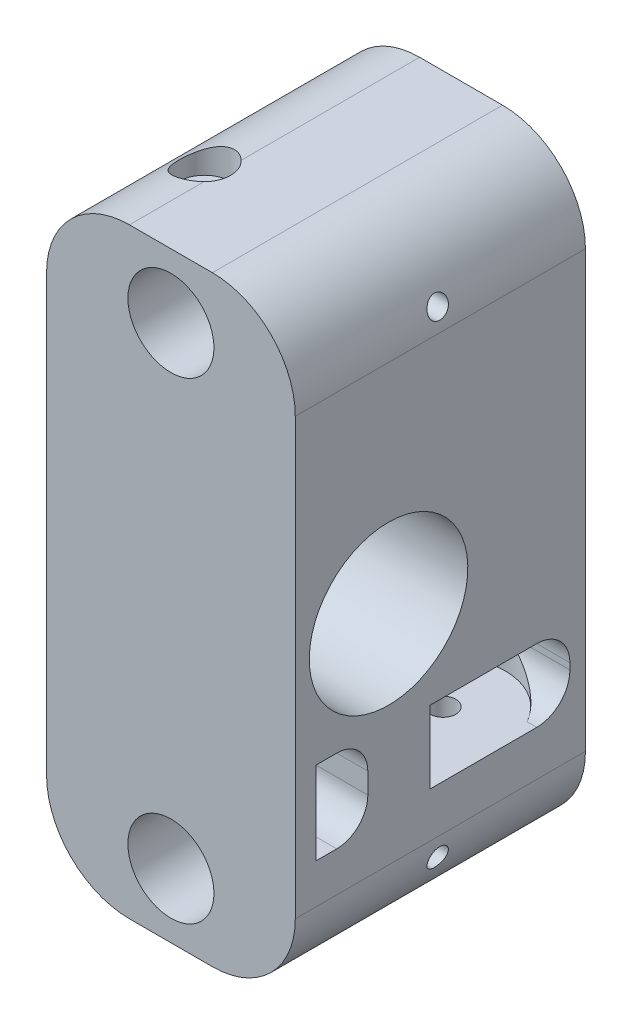
SolidWorks part; units mm, degrees
ref_plane "前视基准面" through (0, 0, 0) normal (0, 0, 1) x (1, 0, 0)
ref_plane "上视基准面" through (0, 0, 0) normal (0, 1, 0) x (1, 0, 0)
ref_plane "右视基准面" through (0, 0, 0) normal (1, 0, 0) x (0, 0, -1)
sketch "草图1" plane through (0, 0, 0) normal (0, 0, 1) x (1, 0, 0)
  line L1 (-12, 29) -> (12, 29)
  line L2 (-12, 29) -> (-12, -29)
  line L3 (-12, -29) -> (12, -29)
  line L4 (12, 29) -> (12, -29)
  line L5 (-12, 29) -> (12, -29) construction
  line L6 (-12, -29) -> (12, 29) construction
  point P0 (0, 0)
  dimension "D1" = 24
  dimension "D2" = 58
extrude "凸台-拉伸1" add sketch "草图1" along normal mid plane 38
sketch "草图2" plane through (12, 0, 0) normal (1, 0, 0) x (0, 0, -1)
  circle A0 centre (0, 0) radius 7.65
  dimension "D1" = 15.3
extrude "切除-拉伸1" cut sketch "草图2" against normal through all
ref_plane "基准面1" through (0, 13.15, 0) normal (0, 1, 0) x (1, 0, 0)
ref_plane "基准面2" through (0, -13.15, 0) normal (0, 1, 0) x (1, 0, 0)
sketch "草图3" plane through (0, 13.15, 0) normal (0, 1, 0) x (1, 0, 0)
  line L0 (0, 0) -> (0, -24.6721) construction
  line L1 (0, 0) -> (-19.2514, 0) construction
  line L2 (-5.75, -7.5) -> (-12, -7.5)
  line L3 (-12, -19) -> (-12, 19) construction
  line L4 (-12, -7.5) -> (-12, 19)
  line L5 (-12, 19) -> (1.75, 19)
  line L6 (12, 19) -> (-12, 19) construction
  line L7 (1.75, 19) -> (1.75, 0)
  circle A2 centre (-5.75, 0) radius 6.5 construction
  circle A3 centre (-5.75, 0) radius 5 construction
  arc A4 (-5.75, -7.5) -> (1.75, 0) centre (-5.75, 0) ccw
  dimension "D1" = 13
  dimension "D2" = 10
  dimension "D3" = 5.75
  dimension "D4" = 15
extrude "切除-拉伸2" cut sketch "草图3" against normal mid plane 7
sketch "草图4" plane through (-12, 0, 0) normal (-1, 0, 0) x (0, 0, 1)
  line L0 (13.2, -13.15) -> (-13.2, -13.15) construction
  line L1 (2, -9.15) -> (7, -9.15)
  line L2 (2, -9.15) -> (2, -17.15)
  line L3 (2, -17.15) -> (7, -17.15)
  line L4 (7, -9.15) -> (7, -17.15)
  line L5 (2, -9.15) -> (7, -17.15) construction
  line L6 (2, -17.15) -> (7, -9.15) construction
  line L7 (0, 0) -> (0, -29.9749) construction
  circle A0 centre (0, -13.15) radius 5 construction
  circle A1 centre (0, -13.15) radius 6.5 construction
  point P0 (4.5, -13.15)
  dimension "D1" = 10
  dimension "D2" = 13
  dimension "D3" = 5
  dimension "D4" = 8
  dimension "D5" = 4.5
extrude "切除-拉伸3" cut sketch "草图4" against normal through all
sketch "草图5" plane through (0, -13.15, 0) normal (0, 1, 0) x (1, 0, 0)
  line L0 (0, 0) -> (0, 26.819) construction
  line L1 (0, 0) -> (24.2805, 0) construction
  line L2 (0, 6.5) -> (23.2538, 6.5) construction
  line L3 (5.75, 4) -> (12, 4)
  line L4 (12, -19) -> (12, 19) construction
  line L5 (-1.75, 11.5) -> (-1.75, 19)
  line L6 (-12, 19) -> (12, 19) construction
  line L7 (-1.75, 19) -> (12, 19)
  line L8 (12, 19) -> (12, 4)
  circle A0 centre (5.75, 11.5) radius 5 construction
  circle A1 centre (5.75, 11.5) radius 6.5 construction
  arc A2 (-1.75, 11.5) -> (5.75, 4) centre (5.75, 11.5) ccw
  dimension "D2" = 10
  dimension "D3" = 13
  dimension "D5" = 15
  dimension "D1" = 6.5
  dimension "D4" = 5.75
extrude "切除-拉伸4" cut sketch "草图5" against normal mid plane 7
sketch "草图6" plane through (0, 0, -19) normal (0, 0, -1) x (-1, 0, 0)
  line L0 (0, 0) -> (0, 34.6715) construction
  line L1 (0, 0) -> (21.1433, 0) construction
  line L4 (-1.75, 16.65) -> (5.75, 16.65) construction
  circle A0 centre (0, 22.8) radius 4.15
  circle A1 centre (0, -22.8) radius 4.15
  point P2 (0, 22.7298)
  point P6 (0, 22.7298)
  point P8 (2.4518, 16.65)
  point P9 (0, 0)
  dimension "D1" = 8.3
  dimension "D2" = 0
  dimension "D3" = 6.15
extrude "切除-拉伸5" cut sketch "草图6" against normal through all
sketch "草图7" plane through (0, 29, 0) normal (0, 1, 0) x (1, 0, 0)
  line L1 (-17.4244, -25.1168) -> (22.3506, -25.1168)
  line L2 (-17.4244, -25.1168) -> (-17.4244, -9)
  line L3 (-17.4244, -9) -> (22.3506, -9)
  line L4 (22.3506, -25.1168) -> (22.3506, -9)
  dimension "D1" = 9
extrude "切除-拉伸6" cut sketch "草图7" against normal through all
sketch "草图8" plane through (0, -29, 0) normal (0, -1, 0) x (1, 0, 0)
  circle A0 centre (5.75, -11.5) radius 1.25
  arc A1 (5.75, -4) -> (-1.75, -11.5) centre (5.75, -11.5) ccw construction
  dimension "D1" = 2.5
extrude "切除-拉伸7" cut sketch "草图8" against normal blind 22
sketch "草图9" plane through (0, 29, 0) normal (0, 1, 0) x (1, 0, 0)
  circle A0 centre (-5.75, 0) radius 1.25
  arc A1 (-5.75, -7.5) -> (1.75, 0) centre (-5.75, 0) ccw construction
  dimension "D1" = 2.5
extrude "切除-拉伸8" cut sketch "草图9" against normal blind 22
fillet "圆角1" radius 8 4 edges at (12, -29, -5) (-12, -29, -5) (-12, 29, -5) (12, 29, -5)
sketch "草图11" plane through (0, -29, 0) normal (0, -1, 0) x (1, 0, 0)
  circle A0 centre (5.75, -11.5) radius 2.5
  circle A1 centre (5.75, -11.5) radius 1.25 construction
  dimension "D1" = 5
extrude "切除-拉伸9" cut sketch "草图11" against normal blind 3
sketch "草图12" plane through (0, 29, 0) normal (0, 1, 0) x (1, 0, 0)
  circle A0 centre (-5.75, 0) radius 2.5
  circle A1 centre (-5.75, 0) radius 1.25 construction
  dimension "D1" = 5
extrude "切除-拉伸10" cut sketch "草图12" against normal blind 3
sketch "草图13" plane through (-12, 0, 0) normal (-1, 0, 0) x (0, 0, 1)
  line L0 (0, 0) -> (-22.1939, 0) construction
  line L1 (0, 0) -> (0, -35.0733) construction
  circle A0 centre (-5, -23) radius 1
  circle A1 centre (-5, 23) radius 1
  point P8 (-12.8729, -15.3558)
  point P9 (-9.2281, -11.3525)
  dimension "D1" = 2
  dimension "D2" = 5
  dimension "D3" = 23
extrude "切除-拉伸11" cut sketch "草图13" against normal through all
fillet "圆角2" radius 3 2 edges at (0, -17.15, 2) (0, -9.15, 2)
sketch "草图14" plane through (0, 9.65, 0) normal (0, 1, 0) x (1, 0, 0)
  line L0 (-5.75, 0) -> (-5.75, 23.4916) construction
  line L2 (-12, -9) -> (-12, 19) construction
  line L3 (-12, 10) -> (-12, 19)
  line L4 (-12, 19) -> (-1.75, 19)
  line L5 (4, 19) -> (-4, 19) construction
  line L7 (-1.75, 10) -> (-1.75, 19)
  line L8 (-1.75, 10) -> (-12, 10)
  line L9 (-0.75, 0) -> (-0.75, 29.5202) construction
  circle A0 centre (-5.75, 0) radius 7.5 construction
  arc A1 (-5.75, -7.5) -> (1.75, 0) centre (-5.75, 0) ccw construction
  circle A2 centre (-5.75, 0) radius 6.5 construction
  circle A3 centre (-5.75, 0) radius 5 construction
  dimension "D1" = 13
  dimension "D2" = 10
  dimension "D3" = 1
  dimension "D4" = 9
extrude "凸台-拉伸2" add sketch "草图14" along normal up to next
fillet "圆角3" radius 3.2 2 edges at (-6.875, 16.65, -10) (-6.875, 9.65, -10)
sketch "草图16" plane through (0, -9.65, 0) normal (0, -1, 0) x (1, 0, 0)
  line L0 (12, -19) -> (12, -17.5)
  line L1 (12, 9) -> (12, -19) construction
  line L2 (12, -17.5) -> (1.75, -17.5)
  line L3 (1.75, -17.5) -> (1.75, -19)
  line L4 (-4, -19) -> (4, -19) construction
  line L5 (1.75, -19) -> (12, -19)
  line L6 (0.75, -11.5) -> (0.75, -29.1863) construction
  circle A0 centre (5.75, -11.5) radius 5 construction
  circle A1 centre (5.75, -11.5) radius 1.25 construction
  circle A2 centre (5.75, -11.5) radius 7.5 construction
  dimension "D1" = 10
  dimension "D2" = 15
  dimension "D3" = 1
  dimension "D4" = 1.5
extrude "凸台-拉伸3" add sketch "草图16" along normal up to next contours L2 L3 L5 L0
fillet "圆角4" radius 3.2 2 edges at (6.875, -16.65, -17.5) (6.875, -9.65, -17.5)
sketch "草图17" plane through (0, -9.65, 0) normal (0, -1, 0) x (1, 0, 0)
  circle A0 centre (5.75, -11.5) radius 6
  circle A1 centre (5.75, -11.5) radius 1.25 construction
  dimension "D1" = 12
extrude "切除-拉伸12" cut sketch "草图17" along normal up to surface (7 mm away) up to face at (5.75, -16.65, -10.25)
